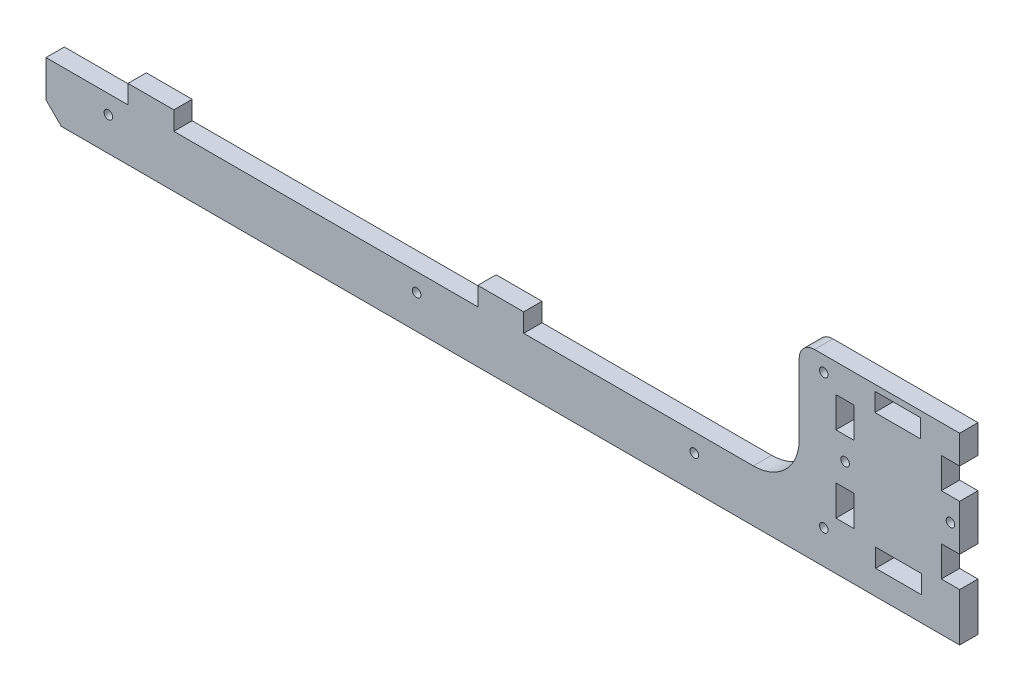
SolidWorks part; units mm, degrees
ref_plane "Front" through (0, 0, 0) normal (0, 0, 1) x (1, 0, 0)
ref_plane "Top" through (0, 0, 0) normal (0, 1, 0) x (1, 0, 0)
ref_plane "Right" through (0, 0, 0) normal (1, 0, 0) x (0, 0, -1)
sketch "Эскиз1" plane through (0, 0, 0) normal (0, 0, 1) x (1, 0, 0)
  line L46 (96.9208, 2) -> (96.9208, 25)
  line L54 (101.9208, 30) -> (149.3892, 30)
  line L55 (149.3892, 30) -> (149.3892, 20.7093)
  line L56 (149.3892, -30) -> (-144.3892, -30)
  line L57 (-144.3892, -30) -> (-149.3892, -25)
  line L58 (-149.3892, -25) -> (-149.3892, -13)
  line L59 (81.9208, -13) -> (6.8114, -13)
  line L72 (121.9208, -16) -> (136.9208, -16)
  line L73 (121.9208, -16) -> (121.9208, -22)
  line L74 (121.9208, -22) -> (136.9208, -22)
  line L75 (136.9208, -16) -> (136.9208, -22)
  line L76 (143.3892, 20.7093) -> (149.3892, 20.7093)
  line L77 (143.3892, 20.7093) -> (143.3892, 10.7093)
  line L78 (143.3892, 10.7093) -> (149.3892, 10.7093)
  line L80 (143.3892, -4.2907) -> (149.3892, -4.2907)
  line L81 (143.3892, -4.2907) -> (143.3892, -14.2907)
  line L82 (143.3892, -14.2907) -> (149.3892, -14.2907)
  line L84 (108.9208, 20.7093) -> (114.9208, 20.7093)
  line L85 (108.9208, 20.7093) -> (108.9208, 10.7093)
  line L86 (108.9208, 10.7093) -> (114.9208, 10.7093)
  line L87 (114.9208, 20.7093) -> (114.9208, 10.7093)
  line L88 (108.9208, -14.2907) -> (114.9208, -14.2907)
  line L89 (108.9208, -14.2907) -> (108.9208, -4.2907)
  line L90 (108.9208, -4.2907) -> (114.9208, -4.2907)
  line L91 (114.9208, -14.2907) -> (114.9208, -4.2907)
  line L92 (121.6558, 28) -> (136.6558, 28)
  line L93 (121.6558, 28) -> (121.6558, 22)
  line L94 (121.6558, 22) -> (136.6558, 22)
  line L95 (136.6558, 28) -> (136.6558, 22)
  line L99 (-135.3886, -19) -> (69.0114, -19) construction
  line L105 (149.3892, 10.7093) -> (149.3892, -4.2907)
  line L106 (149.3892, -14.2907) -> (149.3892, -30)
  line L107 (111.9208, 10.7093) -> (111.9208, -4.2907) construction
  line L108 (146.3892, 10.7093) -> (146.3892, -4.2907) construction
  line L109 (108.9208, 3.2093) -> (149.3892, 3.2405) construction
  line L110 (-128.9886, -2.5796) -> (-128.9886, -38.6586) construction
  line L119 (-28.1886, -6.9168) -> (-28.1886, -36.2533) construction
  line L120 (62.6114, -5.7851) -> (62.6114, -36.2533) construction
  line L121 (-8.1886, -6.9168) -> (-8.1886, -38.6586) construction
  line L123 (-122.5886, -13) -> (-122.5886, -6.9168)
  line L124 (-122.5886, -6.9168) -> (-107.5886, -6.9168)
  line L125 (-107.5886, -13) -> (-107.5886, -6.9168)
  line L126 (-122.5886, -13) -> (-149.3892, -13)
  line L128 (-8.1886, -13) -> (-8.1886, -6.9168)
  line L129 (-8.1886, -6.9168) -> (6.8114, -6.9168)
  line L130 (6.8114, -13) -> (6.8114, -6.9168)
  line L131 (-10.1606, -13) -> (-107.5886, -13)
  line L132 (-8.1886, -13) -> (-10.1606, -13)
  arc A6 (96.9208, 2) -> (81.9208, -13) centre (81.9208, 2) cw
  arc A7 (96.9208, 25) -> (101.9208, 30) centre (101.9208, 25) cw
  circle A8 centre (104.9708, -19) radius 1.4
  circle A9 centre (104.9708, 25) radius 1.4
  circle A10 centre (111.9208, 3.2093) radius 1.4
  circle A11 centre (146.3892, 3.2093) radius 1.4
  circle A12 centre (-128.9886, -19) radius 1.4
  circle A13 centre (-28.1886, -19) radius 1.4
  circle A14 centre (62.6114, -19) radius 1.4
  point P85 (0, 0)
  point P86 (0, 0)
  dimension "D1" = 2.8
  dimension "D2" = 2.8
  dimension "D3" = 2.8
  dimension "D5" = 2.8
  dimension "D6" = 2.8
  dimension "D8" = 15
  dimension "D4" = 20
  dimension "D7" = 15
extrude "Бобышка-Вытянуть1" add sketch "Эскиз1" along normal blind 6
